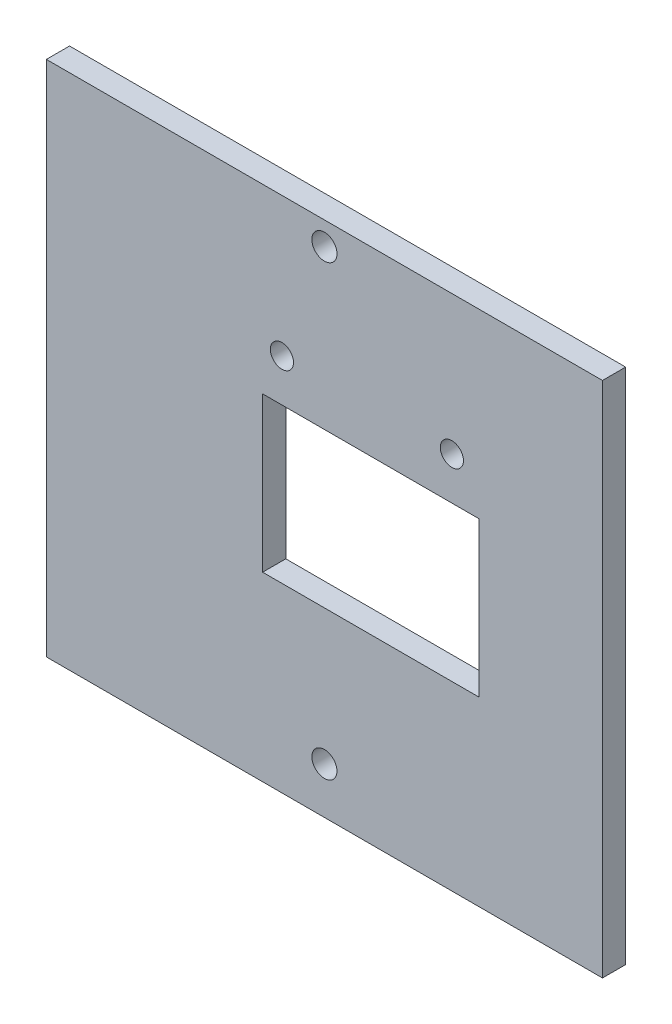
SolidWorks part; units mm, degrees
ref_plane "Alzado" through (0, 0, 0) normal (0, 0, 1) x (1, 0, 0)
ref_plane "Planta" through (0, 0, 0) normal (0, 1, 0) x (1, 0, 0)
ref_plane "Vista lateral" through (0, 0, 0) normal (1, 0, 0) x (0, 0, -1)
sketch "Croquis1" plane through (0, 0, 0) normal (0, 0, 1) x (1, 0, 0)
  line B0 (47.0497, -53.14) -> (47.0497, 13.86)
  line B1 (47.0497, 13.86) -> (119.0497, 13.86)
  line B2 (47.0497, -53.14) -> (119.0497, -53.14)
  line B3 (119.0497, -53.14) -> (119.0497, 13.86)
sketch_block_instance "Bloque-Croquis2-1"
sketch_block "Bloque-Croquis2" parameters "D1"=50, "D2"=59.9093
extrude "Saliente-Extruir1" add sketch "Croquis1" along normal blind 3
sketch "Croquis4" plane through (0, 0, 0) normal (0, 0, -1) x (-1, 0, 0)
  line L0 (-78.0497, -9.64) -> (-75.0497, -9.64)
  line L2 (-78.0497, -9.64) -> (-78.0497, -29.64) construction
  line L3 (-78.0497, -29.64) -> (-103.0497, -29.64)
  line L4 (-103.0497, -9.64) -> (-103.0497, -29.64)
  line L5 (-119.0497, -53.14) -> (-119.0497, 13.86) construction
  line L6 (-47.0497, -53.14) -> (-119.0497, -53.14) construction
  line L11 (-103.0497, -9.64) -> (-78.0497, -9.64)
  line L12 (-103.0497, -9.64) -> (-103.0497, -4.14) construction
  line L13 (-103.0497, -4.14) -> (-78.0497, -4.14) construction
  line L14 (-78.0497, -9.64) -> (-78.0497, -4.14) construction
  line L15 (-75.0497, -9.64) -> (-75.0497, -29.64)
  line L16 (-75.0497, -29.64) -> (-78.0497, -29.64)
  circle A0 centre (-83.0497, -47.14) radius 1.625 construction
  circle A1 centre (-83.0497, 10.86) radius 1.625 construction
  circle A2 centre (-83.0497, -47.14) radius 1.625
  circle A3 centre (-83.0497, 10.86) radius 1.625
  circle A4 centre (-99.5497, -4.14) radius 1.5
  circle A5 centre (-77.5497, -4.14) radius 1.5
  dimension "D6" = 3
  dimension "D7" = 3
  dimension "D8" = 3.5
  dimension "D9" = 0.5
  dimension "D1" = 16
  dimension "D2" = 23.5
  dimension "D3" = 25
  dimension "D4" = 20
  dimension "D5" = 5.5
  dimension "D10" = 3
extrude "Cortar-Extruir2" cut sketch "Croquis4" against normal blind 3
sketch "Croquis5" plane through (0, 0, 0) normal (0, 0, -1) x (-1, 0, 0)
  line L0 (-103.0497, -29.64) -> (-75.0497, -29.64) construction
  line L1 (-75.0497, -9.64) -> (-78.0497, -9.64) construction
  line L2 (-75.0497, -9.64) -> (-75.0497, -29.64) construction
  line L3 (-75.0497, -29.64) -> (-78.0497, -29.64) construction
  line L4 (-78.0497, -9.64) -> (-78.0497, -29.64)
  line L5 (-75.0497, -9.64) -> (-103.0497, -9.64) construction
  line L6 (-101.0497, -28.64) -> (-82.0497, -28.64)
  line L7 (-101.0497, -28.64) -> (-101.0497, -10.64)
  line L8 (-101.0497, -10.64) -> (-82.0497, -10.64)
  line L9 (-82.0497, -28.64) -> (-82.0497, -10.64)
  line L12 (-103.0497, -9.64) -> (-103.0497, -29.64) construction
  dimension "D1" = 3
  dimension "D2" = 1
  dimension "D3" = 2
  dimension "D4" = 19
  dimension "D5" = 18
sketch "Sketch1" plane through (0, 0, 0) normal (0, 0, -1) x (-1, 0, 0)
  line L0 (-83.1641, -11.7027) -> (-83.0942, -11.8472)
  line L1 (-83.0942, -11.8472) -> (-83.0948, -18.3285)
  line L2 (-84.5101, -22.6163) -> (-84.3138, -22.7155)
  line L3 (-84.3138, -22.7155) -> (-84.3138, -19.1831)
  line L4 (-84.3138, -19.1831) -> (-84.3138, -15.6507)
  line L5 (-84.3138, -15.6507) -> (-84.4209, -15.6685)
  line L6 (-93.8632, -16.7274) -> (-93.9366, -16.7434)
  line L7 (-93.9366, -16.7434) -> (-93.9457, -21.4694)
  spline S0 degree 3 poles (-97.4813, -28.221) (-98.4589, -28.08) (-99.3683, -27.4918) (-99.7346, -26.7635) knots 0 0 0 0 1 1 1 1
  spline S1 degree 3 poles (-99.7346, -26.7635) (-99.8636, -26.507) (-99.97, -26.0939) (-99.9692, -25.852) knots 0 0 0 0 1 1 1 1
  spline S2 degree 3 poles (-99.9692, -25.852) (-99.9676, -25.3544) (-99.7498, -24.8284) (-99.3776, -24.4241) knots 0 0 0 0 1 1 1 1
  spline S3 degree 3 poles (-99.3776, -24.4241) (-98.4364, -23.4016) (-96.6968, -23.1394) (-95.3585, -23.8183) knots 0 0 0 0 1 1 1 1
  spline S4 degree 3 poles (-95.3585, -23.8183) (-95.2673, -23.8645) (-95.1849, -23.9023) (-95.1752, -23.9023) knots 0 0 0 0 1 1 1 1
  spline S5 degree 3 poles (-95.1752, -23.9023) (-95.1655, -23.9023) (-95.1575, -21.4859) (-95.1574, -18.5325) knots 0 0 0 0 1 1 1 1
  spline S6 degree 3 poles (-95.1574, -18.5325) (-95.1573, -14.7522) (-95.1466, -13.1236) (-95.1212, -13.0307) knots 0 0 0 0 1 1 1 1
  spline S7 degree 3 poles (-95.1212, -13.0307) (-95.0718, -12.8494) (-94.9575, -12.7079) (-94.8066, -12.641) knots 0 0 0 0 1 1 1 1
  spline S8 degree 3 poles (-94.8066, -12.641) (-94.6483, -12.5709) (-83.7693, -11.3493) (-83.5886, -11.3814) knots 0 0 0 0 1 1 1 1
  spline S9 degree 3 poles (-83.5886, -11.3814) (-83.4121, -11.4128) (-83.2421, -11.5414) (-83.1641, -11.7027) knots 0 0 0 0 1 1 1 1
  spline S10 degree 3 poles (-83.0948, -18.3285) (-83.0955, -25.551) (-83.0792, -25.0483) (-83.3288, -25.5448) knots 0 0 0 0 1 1 1 1
  spline S11 degree 3 poles (-83.3288, -25.5448) (-83.7851, -26.4524) (-84.8745, -27.0368) (-86.1101, -27.0368) knots 0 0 0 0 1 1 1 1
  spline S12 degree 3 poles (-86.1101, -27.0368) (-86.7692, -27.0368) (-87.3291, -26.8912) (-87.8938, -26.5729) knots 0 0 0 0 1 1 1 1
  spline S13 degree 3 poles (-87.8938, -26.5729) (-88.2002, -26.4002) (-88.6579, -25.9603) (-88.8215, -25.6814) knots 0 0 0 0 1 1 1 1
  spline S14 degree 3 poles (-88.8215, -25.6814) (-89.3109, -24.847) (-89.1755, -23.8724) (-88.4706, -23.1558) knots 0 0 0 0 1 1 1 1
  spline S15 degree 3 poles (-88.4706, -23.1558) (-87.5017, -22.1709) (-85.8395, -21.9445) (-84.5101, -22.6163) knots 0 0 0 0 1 1 1 1
  spline S16 degree 3 poles (-84.4209, -15.6685) (-84.4798, -15.6783) (-86.6119, -15.917) (-89.1589, -16.1989) knots 0 0 0 0 1 1 1 1
  spline S17 degree 3 poles (-89.1589, -16.1989) (-91.7059, -16.4808) (-93.8228, -16.7186) (-93.8632, -16.7274) knots 0 0 0 0 1 1 1 1
  spline S18 degree 3 poles (-93.9457, -21.4694) (-93.9544, -25.9747) (-93.9577, -26.2039) (-94.0161, -26.3769) knots 0 0 0 0 1 1 1 1
  spline S19 degree 3 poles (-94.0161, -26.3769) (-94.2438, -27.0516) (-94.702, -27.5543) (-95.3997, -27.895) knots 0 0 0 0 1 1 1 1
  spline S20 degree 3 poles (-95.3997, -27.895) (-96.0298, -28.2027) (-96.7866, -28.3212) (-97.4813, -28.221) knots 0 0 0 0 1 1 1 1
